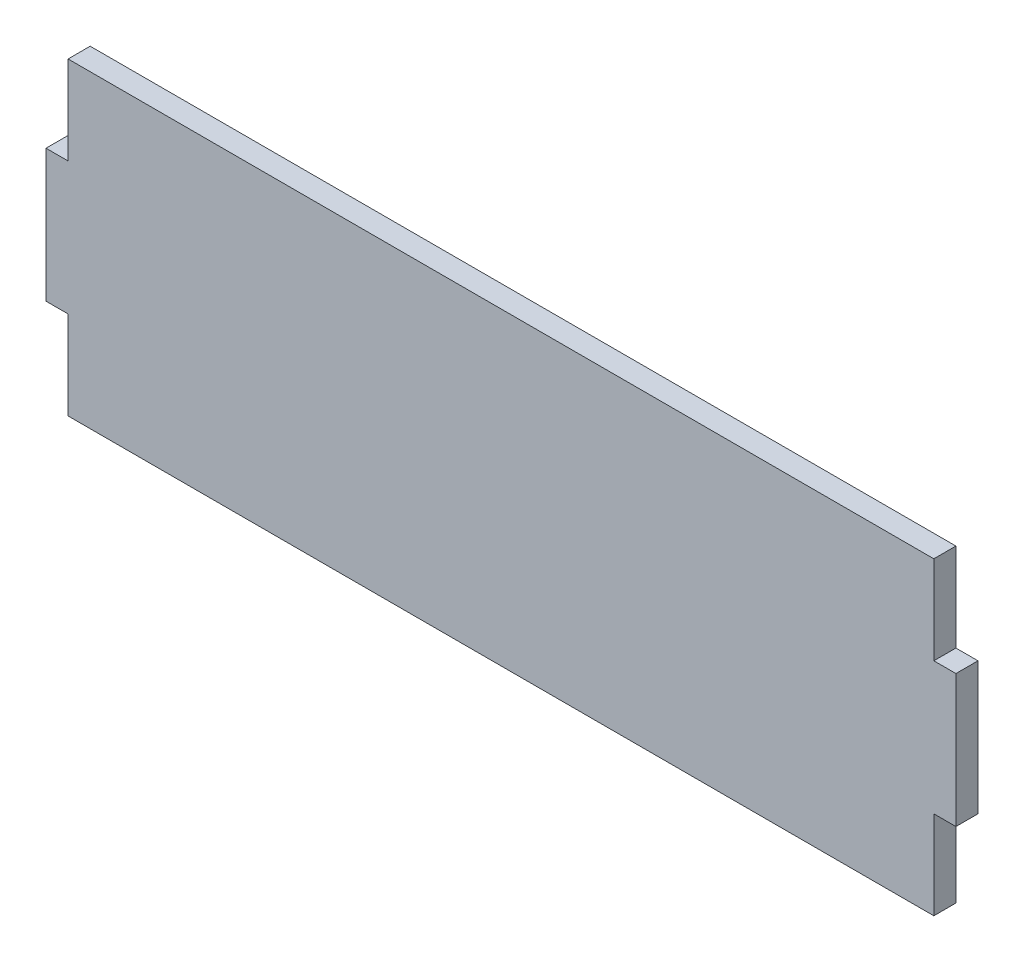
SolidWorks part; units mm, degrees
ref_plane "Plan de face" through (0, 0, 0) normal (0, 0, 1) x (1, 0, 0)
ref_plane "Plan de dessus" through (0, 0, 0) normal (0, 1, 0) x (1, 0, 0)
ref_plane "Plan de droite" through (0, 0, 0) normal (1, 0, 0) x (0, 0, -1)
sketch "Esquisse1" plane through (0, 0, 0) normal (0, 0, 1) x (1, 0, 0)
  line L0 (0, 0) -> (196, 0)
  line L1 (196, 0) -> (196, 20)
  line L2 (196, 20) -> (201, 20)
  line L3 (201, 20) -> (201, 50)
  line L4 (201, 50) -> (196, 50)
  line L5 (196, 50) -> (196, 70)
  line L6 (196, 70) -> (0, 70)
  line L7 (0, 70) -> (0, 50)
  line L8 (0, 50) -> (-5, 50)
  line L9 (-5, 50) -> (-5, 20)
  line L10 (-5, 20) -> (0, 20)
  line L11 (0, 20) -> (0, 0)
  dimension "D1" = 196
  dimension "D2" = 20
  dimension "D3" = 30
  dimension "D4" = 20
  dimension "D5" = 5
extrude "Boss.-Extru.1" add sketch "Esquisse1" along normal blind 5
